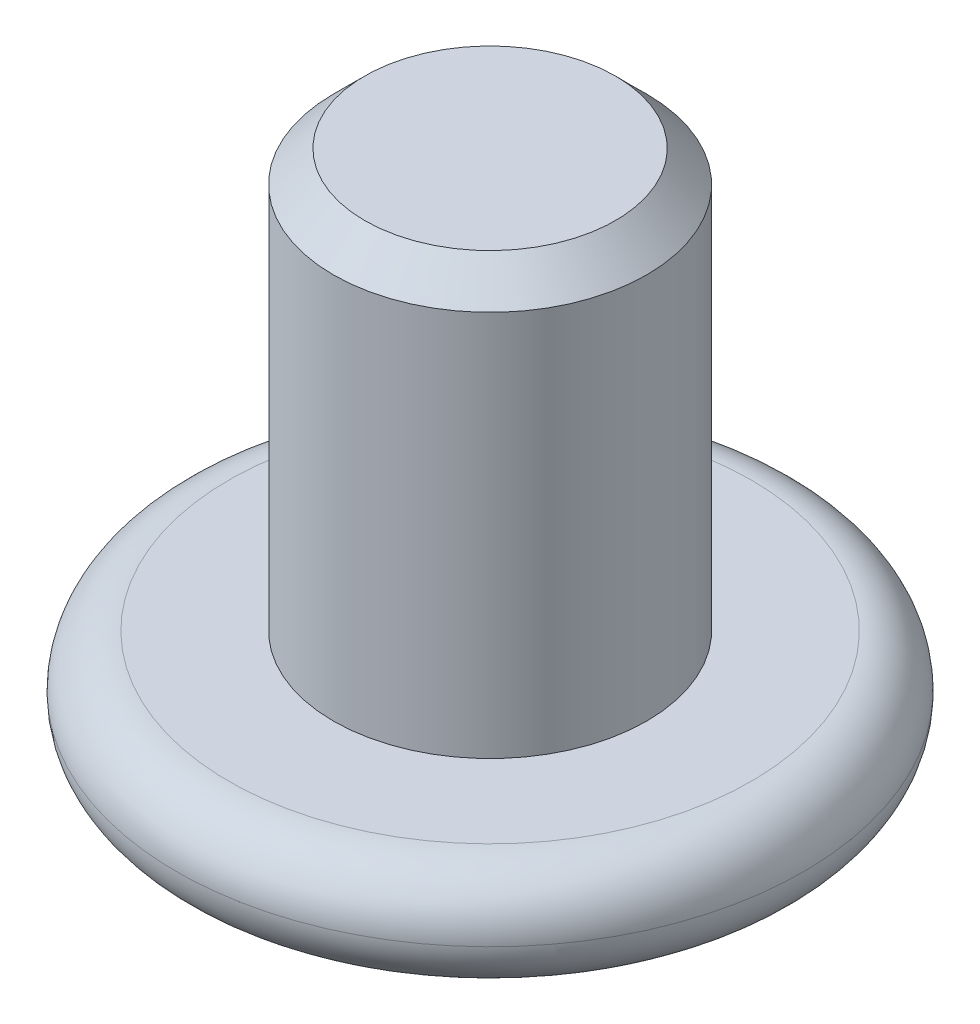
SolidWorks part; units mm, degrees
ref_plane "前视基准面" through (0, 0, 0) normal (0, 0, 1) x (1, 0, 0)
ref_plane "上视基准面" through (0, 0, 0) normal (0, 1, 0) x (1, 0, 0)
ref_plane "右视基准面" through (0, 0, 0) normal (1, 0, 0) x (0, 0, -1)
other "Configuration Table"
sketch "草图2" plane through (0, 0, 0) normal (0, 1, 0) x (1, 0, 0)
  circle A0 centre (0, 0) radius 1.5
extrude "凸台-拉伸1" add sketch "草图2" along normal blind 4
sketch "草图3" plane through (0, 0, 0) normal (0, -1, 0) x (1, 0, 0)
  circle A0 centre (0, 0) radius 3
extrude "凸台-拉伸2" add sketch "草图3" along normal blind 1
fillet "圆角1" radius 0.5 2 edges at (0, 0, -3) (0, -1, -3)
sketch "草图4" plane through (0, -1, 0) normal (0, -1, 0) x (1, 0, 0)
  line L1 (-1.5, -0.2) -> (-0.2, -0.2)
  line L2 (-1.5, 0.2) -> (-0.2, 0.2)
  line L4 (-0.2, 1.5) -> (-0.2, 0.2)
  line L5 (0.2, 1.5) -> (0.2, 0.2)
  line L6 (-0.2, 1.5) -> (0.2, 1.5)
  line L7 (-0.2, -1.5) -> (0.2, -1.5)
  line L8 (-1.5, -0.2) -> (-1.5, 0.2)
  line L9 (1.5, -0.2) -> (1.5, 0.2)
  line L11 (0.2, 0.2) -> (1.5, 0.2)
  line L13 (-0.2, -0.2) -> (-0.2, -1.5)
  line L16 (0.2, -0.2) -> (1.5, -0.2)
  line L18 (0.2, -0.2) -> (0.2, -1.5)
  point P4 (0, 0)
  point P12 (0, 0)
extrude "切除-拉伸2" cut sketch "草图4" against normal blind 0.5
chamfer "倒角1" distance 0.3 angle 45 1 edges at (0, 4, 1.5)
